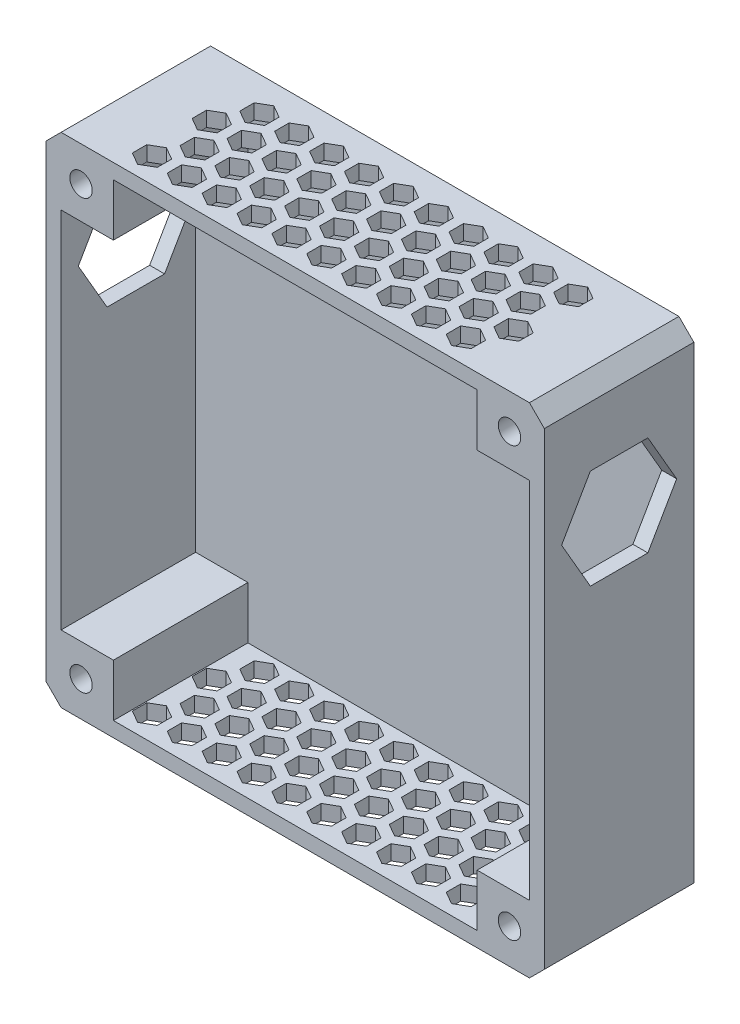
SolidWorks part; units mm, degrees
ref_plane "Front Plane" through (0, 0, 0) normal (0, 0, 1) x (1, 0, 0)
ref_plane "Top Plane" through (0, 0, 0) normal (0, 1, 0) x (1, 0, 0)
ref_plane "Right Plane" through (0, 0, 0) normal (1, 0, 0) x (0, 0, -1)
sketch "Sketch2" plane through (0, 0, 0) normal (0, 0, 1) x (1, 0, 0)
  line L0 (-26.0311, -106.2925) -> (-26.0311, -6.2925)
  line L1 (-26.0311, -6.2925) -> (73.9689, -6.2925)
  line L2 (73.9689, -6.2925) -> (73.9689, -106.2925)
  line L3 (73.9689, -106.2925) -> (-26.0311, -106.2925)
  dimension "D1" = 100
  dimension "D2" = 100
extrude "Boss-Extrude1" add sketch "Sketch2" along normal blind 3
sketch "Sketch3" plane through (0, 0, 3) normal (0, 0, 1) x (1, 0, 0)
  line L0 (73.9689, -6.2925) -> (-26.0311, -6.2925) construction
  line L1 (73.9689, -106.2925) -> (73.9689, -6.2925) construction
  line L3 (-26.0311, -6.2925) -> (-26.0311, -106.2925) construction
  line L4 (-26.0311, -106.2925) -> (73.9689, -106.2925) construction
  line L5 (-26.0311, -6.2925) -> (-26.0311, -106.2925)
  line L6 (-26.0311, -106.2925) -> (73.9689, -106.2925)
  line L7 (73.9689, -106.2925) -> (73.9689, -6.2925)
  line L8 (73.9689, -6.2925) -> (-26.0311, -6.2925)
  line L9 (70.9689, -103.2925) -> (70.9689, -9.2925)
  line L10 (70.9689, -9.2925) -> (-23.0311, -9.2925)
  line L11 (-23.0311, -9.2925) -> (-23.0311, -103.2925)
  line L12 (-23.0311, -103.2925) -> (70.9689, -103.2925)
  line L13 (-26.0311, -56.2925) -> (73.9689, -56.2925) construction
  line L14 (73.9689, -6.2925) -> (60.4689, -6.2925)
  line L15 (73.9689, -6.2925) -> (73.9689, -19.7925)
  line L16 (73.9689, -19.7925) -> (60.4689, -19.7925)
  line L17 (60.4689, -6.2925) -> (60.4689, -19.7925)
  line L18 (23.9689, -6.2925) -> (23.9689, -106.2925) construction
  line L19 (73.9689, -92.7925) -> (60.4689, -92.7925)
  line L20 (60.4689, -106.2925) -> (60.4689, -92.7925)
  line L21 (-12.5311, -106.2925) -> (-12.5311, -92.7925)
  line L22 (-26.0311, -92.7925) -> (-12.5311, -92.7925)
  line L23 (-26.0311, -19.7925) -> (-12.5311, -19.7925)
  line L24 (-12.5311, -6.2925) -> (-12.5311, -19.7925)
  point P18 (0, 0)
  point P26 (0, 0)
  line M9 (-26.0311, -106.2925) -> (73.9689, -106.2925)
  line M10 (73.9689, -106.2925) -> (73.9689, -6.2925)
  line M11 (73.9689, -6.2925) -> (-26.0311, -6.2925)
  line M12 (-26.0311, -6.2925) -> (-26.0311, -106.2925)
  dimension "D2" = 13.5
  dimension "D3" = 13.5
  dimension "D1" = 3
extrude "Boss-Extrude2" add sketch "Sketch3" along normal blind 27 contours L20 L12 L9 L19 | L22 L11 L12 L21 | L24 L10 L11 L23 | L10 L17 L16 L9 | L19 L7 L16 L9 | L8 L24 L10 L17 | L17 L10 L9 L16 L7 M11 | L24 L23 L11 L10 M11 M12 | L23 L5 L22 L11 | L22 L5 L21 L12 L11 M9 | L21 L6 L20 L12 | L20 L6 L19 L9 L12 M10 region at (-19.2811, -6.4834, 3) region at (-24.5311, -56.2925, 3) region at (23.9689, -7.7925, 3) region at (-24.5311, -92.9834, 3) region at (-17.7811, -14.5425, 3) region at (67.2189, -6.4834, 3) region at (-17.7811, -98.0425, 3) region at (65.7189, -14.5425, 3) region at (23.9689, -104.7925, 3) region at (72.4689, -56.2925, 3) region at (60.6598, -104.7925, 3) region at (65.7189, -98.0425, 3)
sketch "Sketch5" plane through (0, -106.2925, 0) normal (0, -1, 0) x (1, 0, 0)
  line L0 (-26.0311, 30) -> (73.9689, 30) construction
  line L1 (-9.7811, 27.8868) -> (-12.2811, 26.4434)
  line L2 (-12.2811, 26.4434) -> (-12.2811, 23.5566)
  line L3 (-12.2811, 23.5566) -> (-9.7811, 22.1132)
  line L4 (-9.7811, 22.1132) -> (-7.2811, 23.5566)
  line L5 (-7.2811, 23.5566) -> (-7.2811, 26.4434)
  line L6 (-7.2811, 26.4434) -> (-9.7811, 27.8868)
  line L7 (-0.2811, 23.5566) -> (-0.2811, 26.4434)
  line L8 (-26.0311, 30) -> (-26.0311, 0) construction
  line L15 (-6.2811, 21.8246) -> (-8.7811, 20.3812)
  line L16 (-8.7811, 20.3812) -> (-8.7811, 17.4944)
  line L17 (-8.7811, 17.4944) -> (-6.2811, 16.0511)
  line L18 (-6.2811, 16.0511) -> (-3.7811, 17.4944)
  line L19 (-3.7811, 17.4944) -> (-3.7811, 20.3812)
  line L20 (-3.7811, 20.3812) -> (-6.2811, 21.8246)
  line L21 (-2.7811, 22.1132) -> (-0.2811, 23.5566)
  line L22 (-5.2811, 23.5566) -> (-2.7811, 22.1132)
  line L23 (-5.2811, 26.4434) -> (-5.2811, 23.5566)
  line L24 (-2.7811, 27.8868) -> (-5.2811, 26.4434)
  line L25 (-0.2811, 26.4434) -> (-2.7811, 27.8868)
  line L26 (3.2189, 20.3812) -> (0.7189, 21.8246)
  line L27 (3.2189, 17.4944) -> (3.2189, 20.3812)
  line L28 (0.7189, 16.0511) -> (3.2189, 17.4944)
  line L29 (-1.7811, 17.4944) -> (0.7189, 16.0511)
  line L30 (-1.7811, 20.3812) -> (-1.7811, 17.4944)
  line L31 (0.7189, 21.8246) -> (-1.7811, 20.3812)
  line L32 (6.7189, 23.5566) -> (6.7189, 26.4434)
  line L33 (4.2189, 22.1132) -> (6.7189, 23.5566)
  line L34 (1.7189, 23.5566) -> (4.2189, 22.1132)
  line L35 (1.7189, 26.4434) -> (1.7189, 23.5566)
  line L36 (4.2189, 27.8868) -> (1.7189, 26.4434)
  line L37 (6.7189, 26.4434) -> (4.2189, 27.8868)
  line L38 (10.2189, 20.3812) -> (7.7189, 21.8246)
  line L39 (10.2189, 17.4944) -> (10.2189, 20.3812)
  line L40 (7.7189, 16.0511) -> (10.2189, 17.4944)
  line L41 (5.2189, 17.4944) -> (7.7189, 16.0511)
  line L42 (5.2189, 20.3812) -> (5.2189, 17.4944)
  line L43 (7.7189, 21.8246) -> (5.2189, 20.3812)
  line L44 (13.7189, 23.5566) -> (13.7189, 26.4434)
  line L45 (11.2189, 22.1132) -> (13.7189, 23.5566)
  line L46 (8.7189, 23.5566) -> (11.2189, 22.1132)
  line L47 (8.7189, 26.4434) -> (8.7189, 23.5566)
  line L48 (11.2189, 27.8868) -> (8.7189, 26.4434)
  line L49 (13.7189, 26.4434) -> (11.2189, 27.8868)
  line L50 (17.2189, 20.3812) -> (14.7189, 21.8246)
  line L51 (17.2189, 17.4944) -> (17.2189, 20.3812)
  line L52 (14.7189, 16.0511) -> (17.2189, 17.4944)
  line L53 (12.2189, 17.4944) -> (14.7189, 16.0511)
  line L54 (12.2189, 20.3812) -> (12.2189, 17.4944)
  line L55 (14.7189, 21.8246) -> (12.2189, 20.3812)
  line L56 (20.7189, 23.5566) -> (20.7189, 26.4434)
  line L57 (18.2189, 22.1132) -> (20.7189, 23.5566)
  line L58 (15.7189, 23.5566) -> (18.2189, 22.1132)
  line L59 (15.7189, 26.4434) -> (15.7189, 23.5566)
  line L60 (18.2189, 27.8868) -> (15.7189, 26.4434)
  line L61 (20.7189, 26.4434) -> (18.2189, 27.8868)
  line L62 (24.2189, 20.3812) -> (21.7189, 21.8246)
  line L63 (24.2189, 17.4944) -> (24.2189, 20.3812)
  line L64 (21.7189, 16.0511) -> (24.2189, 17.4944)
  line L65 (19.2189, 17.4944) -> (21.7189, 16.0511)
  line L66 (19.2189, 20.3812) -> (19.2189, 17.4944)
  line L67 (21.7189, 21.8246) -> (19.2189, 20.3812)
  line L68 (27.7189, 23.5566) -> (27.7189, 26.4434)
  line L69 (25.2189, 22.1132) -> (27.7189, 23.5566)
  line L70 (22.7189, 23.5566) -> (25.2189, 22.1132)
  line L71 (22.7189, 26.4434) -> (22.7189, 23.5566)
  line L72 (25.2189, 27.8868) -> (22.7189, 26.4434)
  line L73 (27.7189, 26.4434) -> (25.2189, 27.8868)
  line L74 (31.2189, 20.3812) -> (28.7189, 21.8246)
  line L75 (31.2189, 17.4944) -> (31.2189, 20.3812)
  line L76 (28.7189, 16.0511) -> (31.2189, 17.4944)
  line L77 (26.2189, 17.4944) -> (28.7189, 16.0511)
  line L78 (26.2189, 20.3812) -> (26.2189, 17.4944)
  line L79 (28.7189, 21.8246) -> (26.2189, 20.3812)
  line L80 (34.7189, 23.5566) -> (34.7189, 26.4434)
  line L81 (32.2189, 22.1132) -> (34.7189, 23.5566)
  line L82 (29.7189, 23.5566) -> (32.2189, 22.1132)
  line L83 (29.7189, 26.4434) -> (29.7189, 23.5566)
  line L84 (32.2189, 27.8868) -> (29.7189, 26.4434)
  line L85 (34.7189, 26.4434) -> (32.2189, 27.8868)
  line L86 (38.2189, 20.3812) -> (35.7189, 21.8246)
  line L87 (38.2189, 17.4944) -> (38.2189, 20.3812)
  line L88 (35.7189, 16.0511) -> (38.2189, 17.4944)
  line L89 (33.2189, 17.4944) -> (35.7189, 16.0511)
  line L90 (33.2189, 20.3812) -> (33.2189, 17.4944)
  line L91 (35.7189, 21.8246) -> (33.2189, 20.3812)
  line L92 (41.7189, 23.5566) -> (41.7189, 26.4434)
  line L93 (39.2189, 22.1132) -> (41.7189, 23.5566)
  line L94 (36.7189, 23.5566) -> (39.2189, 22.1132)
  line L95 (36.7189, 26.4434) -> (36.7189, 23.5566)
  line L96 (39.2189, 27.8868) -> (36.7189, 26.4434)
  line L97 (41.7189, 26.4434) -> (39.2189, 27.8868)
  line L98 (45.2189, 20.3812) -> (42.7189, 21.8246)
  line L99 (45.2189, 17.4944) -> (45.2189, 20.3812)
  line L100 (42.7189, 16.0511) -> (45.2189, 17.4944)
  line L101 (40.2189, 17.4944) -> (42.7189, 16.0511)
  line L102 (40.2189, 20.3812) -> (40.2189, 17.4944)
  line L103 (42.7189, 21.8246) -> (40.2189, 20.3812)
  line L104 (48.7189, 23.5566) -> (48.7189, 26.4434)
  line L105 (46.2189, 22.1132) -> (48.7189, 23.5566)
  line L106 (43.7189, 23.5566) -> (46.2189, 22.1132)
  line L107 (43.7189, 26.4434) -> (43.7189, 23.5566)
  line L108 (46.2189, 27.8868) -> (43.7189, 26.4434)
  line L109 (48.7189, 26.4434) -> (46.2189, 27.8868)
  line L110 (52.2189, 20.3812) -> (49.7189, 21.8246)
  line L111 (52.2189, 17.4944) -> (52.2189, 20.3812)
  line L112 (49.7189, 16.0511) -> (52.2189, 17.4944)
  line L113 (47.2189, 17.4944) -> (49.7189, 16.0511)
  line L114 (47.2189, 20.3812) -> (47.2189, 17.4944)
  line L115 (49.7189, 21.8246) -> (47.2189, 20.3812)
  line L116 (55.7189, 23.5566) -> (55.7189, 26.4434)
  line L117 (53.2189, 22.1132) -> (55.7189, 23.5566)
  line L118 (50.7189, 23.5566) -> (53.2189, 22.1132)
  line L119 (50.7189, 26.4434) -> (50.7189, 23.5566)
  line L120 (53.2189, 27.8868) -> (50.7189, 26.4434)
  line L121 (55.7189, 26.4434) -> (53.2189, 27.8868)
  line L122 (59.2189, 20.3812) -> (56.7189, 21.8246)
  line L123 (59.2189, 17.4944) -> (59.2189, 20.3812)
  line L124 (56.7189, 16.0511) -> (59.2189, 17.4944)
  line L125 (54.2189, 17.4944) -> (56.7189, 16.0511)
  line L126 (54.2189, 20.3812) -> (54.2189, 17.4944)
  line L127 (56.7189, 21.8246) -> (54.2189, 20.3812)
  line L128 (-0.2811, 11.5566) -> (-0.2811, 14.4434)
  line L129 (-2.7811, 10.1132) -> (-0.2811, 11.5566)
  line L130 (-5.2811, 11.5566) -> (-2.7811, 10.1132)
  line L131 (-5.2811, 14.4434) -> (-5.2811, 11.5566)
  line L132 (-2.7811, 15.8868) -> (-5.2811, 14.4434)
  line L133 (-0.2811, 14.4434) -> (-2.7811, 15.8868)
  line L134 (3.2189, 8.3812) -> (0.7189, 9.8246)
  line L135 (3.2189, 5.4944) -> (3.2189, 8.3812)
  line L136 (0.7189, 4.0511) -> (3.2189, 5.4944)
  line L137 (-1.7811, 5.4944) -> (0.7189, 4.0511)
  line L138 (-1.7811, 8.3812) -> (-1.7811, 5.4944)
  line L139 (0.7189, 9.8246) -> (-1.7811, 8.3812)
  line L140 (6.7189, 11.5566) -> (6.7189, 14.4434)
  line L141 (4.2189, 10.1132) -> (6.7189, 11.5566)
  line L142 (1.7189, 11.5566) -> (4.2189, 10.1132)
  line L143 (1.7189, 14.4434) -> (1.7189, 11.5566)
  line L144 (4.2189, 15.8868) -> (1.7189, 14.4434)
  line L145 (6.7189, 14.4434) -> (4.2189, 15.8868)
  line L146 (10.2189, 8.3812) -> (7.7189, 9.8246)
  line L147 (10.2189, 5.4944) -> (10.2189, 8.3812)
  line L148 (7.7189, 4.0511) -> (10.2189, 5.4944)
  line L149 (5.2189, 5.4944) -> (7.7189, 4.0511)
  line L150 (5.2189, 8.3812) -> (5.2189, 5.4944)
  line L151 (7.7189, 9.8246) -> (5.2189, 8.3812)
  line L152 (13.7189, 11.5566) -> (13.7189, 14.4434)
  line L153 (11.2189, 10.1132) -> (13.7189, 11.5566)
  line L154 (8.7189, 11.5566) -> (11.2189, 10.1132)
  line L155 (8.7189, 14.4434) -> (8.7189, 11.5566)
  line L156 (11.2189, 15.8868) -> (8.7189, 14.4434)
  line L157 (13.7189, 14.4434) -> (11.2189, 15.8868)
  line L158 (17.2189, 8.3812) -> (14.7189, 9.8246)
  line L159 (17.2189, 5.4944) -> (17.2189, 8.3812)
  line L160 (14.7189, 4.0511) -> (17.2189, 5.4944)
  line L161 (12.2189, 5.4944) -> (14.7189, 4.0511)
  line L162 (12.2189, 8.3812) -> (12.2189, 5.4944)
  line L163 (14.7189, 9.8246) -> (12.2189, 8.3812)
  line L164 (20.7189, 11.5566) -> (20.7189, 14.4434)
  line L165 (18.2189, 10.1132) -> (20.7189, 11.5566)
  line L166 (15.7189, 11.5566) -> (18.2189, 10.1132)
  line L167 (15.7189, 14.4434) -> (15.7189, 11.5566)
  line L168 (18.2189, 15.8868) -> (15.7189, 14.4434)
  line L169 (20.7189, 14.4434) -> (18.2189, 15.8868)
  line L170 (24.2189, 8.3812) -> (21.7189, 9.8246)
  line L171 (24.2189, 5.4944) -> (24.2189, 8.3812)
  line L172 (21.7189, 4.0511) -> (24.2189, 5.4944)
  line L173 (19.2189, 5.4944) -> (21.7189, 4.0511)
  line L174 (19.2189, 8.3812) -> (19.2189, 5.4944)
  line L175 (21.7189, 9.8246) -> (19.2189, 8.3812)
  line L176 (27.7189, 11.5566) -> (27.7189, 14.4434)
  line L177 (25.2189, 10.1132) -> (27.7189, 11.5566)
  line L178 (22.7189, 11.5566) -> (25.2189, 10.1132)
  line L179 (22.7189, 14.4434) -> (22.7189, 11.5566)
  line L180 (25.2189, 15.8868) -> (22.7189, 14.4434)
  line L181 (27.7189, 14.4434) -> (25.2189, 15.8868)
  line L182 (31.2189, 8.3812) -> (28.7189, 9.8246)
  line L183 (31.2189, 5.4944) -> (31.2189, 8.3812)
  line L184 (28.7189, 4.0511) -> (31.2189, 5.4944)
  line L185 (26.2189, 5.4944) -> (28.7189, 4.0511)
  line L186 (26.2189, 8.3812) -> (26.2189, 5.4944)
  line L187 (28.7189, 9.8246) -> (26.2189, 8.3812)
  line L188 (34.7189, 11.5566) -> (34.7189, 14.4434)
  line L189 (32.2189, 10.1132) -> (34.7189, 11.5566)
  line L190 (29.7189, 11.5566) -> (32.2189, 10.1132)
  line L191 (29.7189, 14.4434) -> (29.7189, 11.5566)
  line L192 (32.2189, 15.8868) -> (29.7189, 14.4434)
  line L193 (34.7189, 14.4434) -> (32.2189, 15.8868)
  line L194 (38.2189, 8.3812) -> (35.7189, 9.8246)
  line L195 (38.2189, 5.4944) -> (38.2189, 8.3812)
  line L196 (35.7189, 4.0511) -> (38.2189, 5.4944)
  line L197 (33.2189, 5.4944) -> (35.7189, 4.0511)
  line L198 (33.2189, 8.3812) -> (33.2189, 5.4944)
  line L199 (35.7189, 9.8246) -> (33.2189, 8.3812)
  line L200 (41.7189, 11.5566) -> (41.7189, 14.4434)
  line L201 (39.2189, 10.1132) -> (41.7189, 11.5566)
  line L202 (36.7189, 11.5566) -> (39.2189, 10.1132)
  line L203 (36.7189, 14.4434) -> (36.7189, 11.5566)
  line L204 (39.2189, 15.8868) -> (36.7189, 14.4434)
  line L205 (41.7189, 14.4434) -> (39.2189, 15.8868)
  line L206 (45.2189, 8.3812) -> (42.7189, 9.8246)
  line L207 (45.2189, 5.4944) -> (45.2189, 8.3812)
  line L208 (42.7189, 4.0511) -> (45.2189, 5.4944)
  line L209 (40.2189, 5.4944) -> (42.7189, 4.0511)
  line L210 (40.2189, 8.3812) -> (40.2189, 5.4944)
  line L211 (42.7189, 9.8246) -> (40.2189, 8.3812)
  line L212 (48.7189, 11.5566) -> (48.7189, 14.4434)
  line L213 (46.2189, 10.1132) -> (48.7189, 11.5566)
  line L214 (43.7189, 11.5566) -> (46.2189, 10.1132)
  line L215 (43.7189, 14.4434) -> (43.7189, 11.5566)
  line L216 (46.2189, 15.8868) -> (43.7189, 14.4434)
  line L217 (48.7189, 14.4434) -> (46.2189, 15.8868)
  line L218 (52.2189, 8.3812) -> (49.7189, 9.8246)
  line L219 (52.2189, 5.4944) -> (52.2189, 8.3812)
  line L220 (49.7189, 4.0511) -> (52.2189, 5.4944)
  line L221 (47.2189, 5.4944) -> (49.7189, 4.0511)
  line L222 (47.2189, 8.3812) -> (47.2189, 5.4944)
  line L223 (49.7189, 9.8246) -> (47.2189, 8.3812)
  line L224 (55.7189, 11.5566) -> (55.7189, 14.4434)
  line L225 (53.2189, 10.1132) -> (55.7189, 11.5566)
  line L226 (50.7189, 11.5566) -> (53.2189, 10.1132)
  line L227 (50.7189, 14.4434) -> (50.7189, 11.5566)
  line L228 (53.2189, 15.8868) -> (50.7189, 14.4434)
  line L229 (55.7189, 14.4434) -> (53.2189, 15.8868)
  line L230 (59.2189, 8.3812) -> (56.7189, 9.8246)
  line L231 (59.2189, 5.4944) -> (59.2189, 8.3812)
  line L232 (56.7189, 4.0511) -> (59.2189, 5.4944)
  line L233 (54.2189, 5.4944) -> (56.7189, 4.0511)
  line L234 (54.2189, 8.3812) -> (54.2189, 5.4944)
  line L235 (56.7189, 9.8246) -> (54.2189, 8.3812)
  line L236 (-7.2811, 11.5566) -> (-7.2811, 14.4434)
  line L237 (-9.7811, 10.1132) -> (-7.2811, 11.5566)
  line L238 (-12.2811, 11.5566) -> (-9.7811, 10.1132)
  line L239 (-12.2811, 14.4434) -> (-12.2811, 11.5566)
  line L240 (-9.7811, 15.8868) -> (-12.2811, 14.4434)
  line L241 (-7.2811, 14.4434) -> (-9.7811, 15.8868)
  line L242 (-3.7811, 8.3812) -> (-6.2811, 9.8246)
  line L243 (-3.7811, 5.4944) -> (-3.7811, 8.3812)
  line L244 (-6.2811, 4.0511) -> (-3.7811, 5.4944)
  line L245 (-8.7811, 5.4944) -> (-6.2811, 4.0511)
  line L246 (-8.7811, 8.3812) -> (-8.7811, 5.4944)
  line L247 (-6.2811, 9.8246) -> (-8.7811, 8.3812)
  circle A0 centre (-9.7811, 25) radius 2.5 construction
  circle A1 centre (-6.2811, 18.9378) radius 2.5 construction
  point P13 (-8.5311, 22.8349)
  dimension "D1" = 5
  dimension "D5" = 2
  dimension "D4" = 3.5
  dimension "D2" = 5
  dimension "D3" = 16.25
  dimension "D6" = 10
  dimension "D7" = 2
extrude "Cut-Extrude1" cut sketch "Sketch5" against normal through all
sketch "Sketch6" plane through (73.9689, 0, 0) normal (1, 0, 0) x (0, 0, -1)
  line L0 (0, -56.2925) -> (-30, -56.2925) construction
  line L3 (-15, -56.2925) -> (-15, -6.2925) construction
  line L6 (-26.547, -31.2925) -> (-20.7735, -41.2925)
  line L7 (-20.7735, -41.2925) -> (-9.2265, -41.2925)
  line L8 (-9.2265, -41.2925) -> (-3.453, -31.2925)
  line L9 (-3.453, -31.2925) -> (-9.2265, -21.2925)
  line L10 (-9.2265, -21.2925) -> (-20.7735, -21.2925)
  line L11 (-20.7735, -21.2925) -> (-26.547, -31.2925)
  circle A0 centre (-15, -31.2925) radius 10 construction
  dimension "D2" = 20
  dimension "D1" = 25
extrude "Cut-Extrude2" cut sketch "Sketch6" against normal through all
sketch "Sketch7" plane through (0, 0, 0) normal (0, 0, -1) x (-1, 0, 0)
  line L0 (-73.9689, -92.2925) -> (-59.9689, -92.2925)
  line L1 (-73.9689, -106.2925) -> (-73.9689, -6.2925) construction
  line L2 (-59.9689, -92.2925) -> (-59.9689, -106.2925)
  line L3 (26.0311, -106.2925) -> (-73.9689, -106.2925) construction
  line L4 (-66.9689, -92.2925) -> (-66.9689, -106.2925) construction
  line L5 (-59.9689, -99.2925) -> (-73.9689, -99.2925) construction
  line L6 (-23.9689, -106.2925) -> (-23.9689, -6.2925) construction
  line L7 (-72.1651, -99.2925) -> (-69.567, -103.7925)
  line L8 (-69.567, -103.7925) -> (-64.3708, -103.7925)
  line L9 (-64.3708, -103.7925) -> (-61.7728, -99.2925)
  line L10 (-61.7728, -99.2925) -> (-64.3708, -94.7925)
  line L11 (-64.3708, -94.7925) -> (-69.567, -94.7925)
  line L12 (-69.567, -94.7925) -> (-72.1651, -99.2925)
  line L14 (-23.9689, -56.2925) -> (26.0311, -56.2925) construction
  line L16 (12.0311, -99.2925) -> (26.0311, -99.2925) construction
  line L17 (19.0311, -92.2925) -> (19.0311, -106.2925) construction
  line L18 (21.6292, -94.7925) -> (24.2272, -99.2925)
  line L19 (16.433, -94.7925) -> (21.6292, -94.7925)
  line L20 (13.8349, -99.2925) -> (16.433, -94.7925)
  line L21 (16.433, -103.7925) -> (13.8349, -99.2925)
  line L22 (21.6292, -103.7925) -> (16.433, -103.7925)
  line L23 (24.2272, -99.2925) -> (21.6292, -103.7925)
  line L24 (12.0311, -92.2925) -> (12.0311, -106.2925)
  line L25 (26.0311, -92.2925) -> (12.0311, -92.2925)
  line L26 (19.0311, -20.2925) -> (19.0311, -6.2925) construction
  line L27 (12.0311, -13.2925) -> (26.0311, -13.2925) construction
  line L28 (-59.9689, -13.2925) -> (-73.9689, -13.2925) construction
  line L29 (-66.9689, -20.2925) -> (-66.9689, -6.2925) construction
  line L30 (26.0311, -20.2925) -> (12.0311, -20.2925)
  line L31 (12.0311, -20.2925) -> (12.0311, -6.2925)
  line L32 (24.2272, -13.2925) -> (21.6292, -8.7925)
  line L33 (21.6292, -8.7925) -> (16.433, -8.7925)
  line L34 (16.433, -8.7925) -> (13.8349, -13.2925)
  line L35 (13.8349, -13.2925) -> (16.433, -17.7925)
  line L36 (16.433, -17.7925) -> (21.6292, -17.7925)
  line L37 (21.6292, -17.7925) -> (24.2272, -13.2925)
  line L38 (-69.567, -17.7925) -> (-72.1651, -13.2925)
  line L39 (-64.3708, -17.7925) -> (-69.567, -17.7925)
  line L40 (-61.7728, -13.2925) -> (-64.3708, -17.7925)
  line L41 (-64.3708, -8.7925) -> (-61.7728, -13.2925)
  line L42 (-69.567, -8.7925) -> (-64.3708, -8.7925)
  line L43 (-72.1651, -13.2925) -> (-69.567, -8.7925)
  line L44 (-59.9689, -20.2925) -> (-59.9689, -6.2925)
  line L45 (-73.9689, -20.2925) -> (-59.9689, -20.2925)
  circle A0 centre (-66.9689, -99.2925) radius 4.5 construction
  circle A1 centre (19.0311, -99.2925) radius 4.5 construction
  circle A2 centre (19.0311, -13.2925) radius 4.5 construction
  circle A3 centre (-66.9689, -13.2925) radius 4.5 construction
  circle A4 centre (-66.9689, -13.2925) radius 4.5
  circle A5 centre (-66.9689, -13.2925) radius 2.25
  circle A6 centre (19.0311, -13.2925) radius 2.25
  circle A7 centre (19.0311, -99.2925) radius 2.25
  circle A8 centre (-66.9689, -99.2925) radius 2.25
  dimension "D3" = 9
  dimension "D4" = 4.5
  dimension "D1" = 14
  dimension "D2" = 14
extrude "Cut-Extrude3" cut sketch "Sketch7" against normal blind 15 contours L43 L38 L39 L40 L41 L42 | L36 L37 L32 L33 L34 L35 | L23 L18 L19 L20 L21 L22 | L11 L12 L7 L8 L9 L10 | L38 L43 L42 L41 L40 L39 | A6 | A8 | A7 region at (70.747, -97.1112, 0) region at (-22.8091, -97.1112, 0) region at (-22.8091, -15.4737, 0) region at (69.2944, -9.2645, 0)
extrude "Cut-Extrude4" cut sketch "Sketch7<3>" against normal through all contours A5 | A6 | A7 | A8 region at (66.9689, -13.2925, 0) region at (-19.0311, -13.2925, 0) region at (-19.0311, -99.2925, 0) region at (66.9689, -99.2925, 0)
sketch "Sketch7<3>" plane through (0, 0, 0) normal (0, 0, -1) x (-1, 0, 0) same geometry as "Sketch7"
sketch "Sketch8" plane through (0, 0, 15) normal (0, 0, -1) x (-1, 0, 0)
  line L0 (-23.9689, -6.2925) -> (-23.9689, -106.2925) construction
  line L1 (-73.9689, -6.2925) -> (26.0311, -6.2925) construction
  line L2 (26.0311, -56.2925) -> (-73.9689, -56.2925) construction
  line L3 (26.0311, -6.2925) -> (26.0311, -106.2925) construction
  line L4 (-73.9689, -106.2925) -> (-73.9689, -6.2925) construction
  line L5 (26.0311, -106.2925) -> (-73.9689, -106.2925) construction
  circle A0 centre (-66.9689, -13.2925) radius 2.65
  circle A1 centre (-66.9689, -13.2925) radius 2.25 construction
  circle A4 centre (19.0311, -13.2925) radius 2.65
  circle A5 centre (-66.9689, -99.2925) radius 2.65
  circle A6 centre (19.0311, -99.2925) radius 2.65
  dimension "D1" = 0.4
extrude "Boss-Extrude3" add sketch "Sketch8" along normal blind 15
chamfer "Chamfer1" distance 3 angle 45 4 edges at (73.9689, -106.2925, 15) (73.9689, -6.2925, 15) (-26.0311, -6.2925, 15) (-26.0311, -106.2925, 15)
equation "\"R\"= 125mm"
